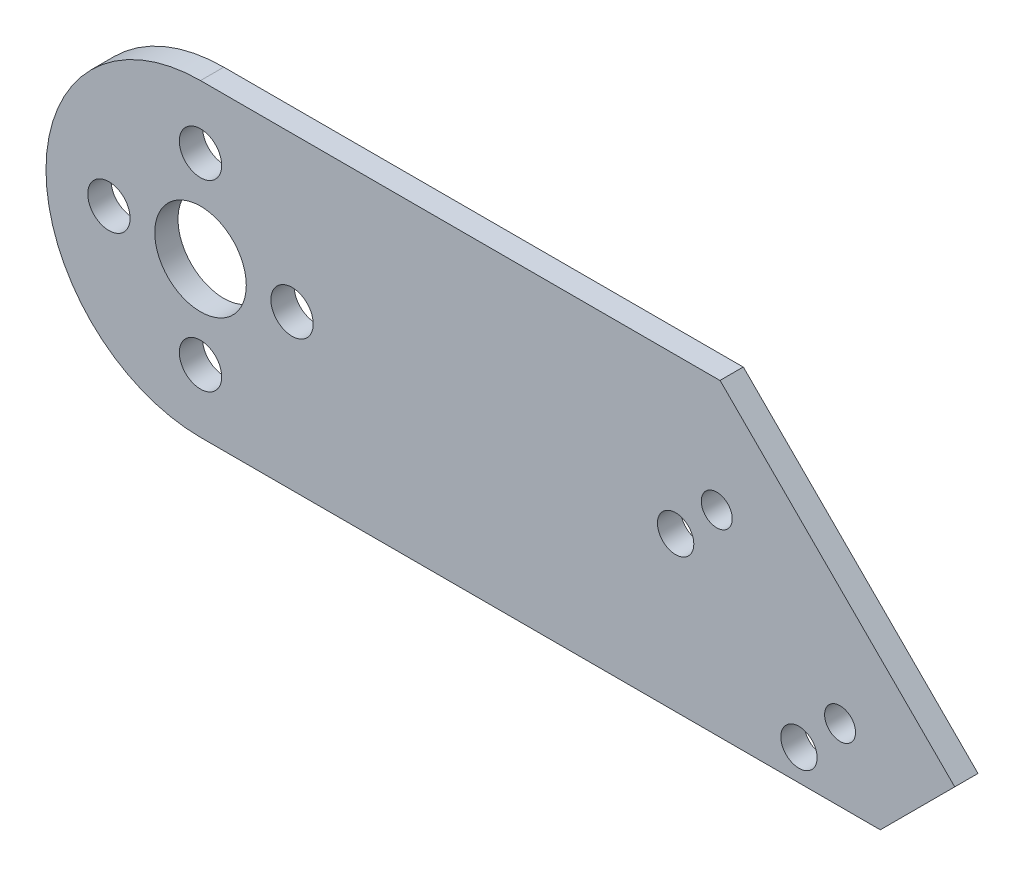
SolidWorks part; units mm, degrees
note: '?' marks a value the reader was unsure of.
ref_plane "Front" through (0, 0, 0) normal (0, 0, 1) x (1, 0, 0)
ref_plane "Top" through (0, 0, 0) normal (0, 1, 0) x (1, 0, 0)
ref_plane "Right" through (0, 0, 0) normal (1, 0, 0) x (0, 0, -1)
ref_axis "side-side" through (80.9, 0, 0) along (-1, 0, 0)?
ref_axis "up-down" through (0, 50, 0) along (0, -1, 0)?
ref_axis "front-back" through (0, 0, -80.9) along (0, 0, 1)?
sketch "Sketch1" plane through (0, 0, 0) normal (0, 0, 1) x (1, 0, 0)
  line L10 (45.3962, 13.5101) -> (45.3862, 13.5)
  line L11 (65.9023, -6.996) -> (45.3962, 13.5101)
  line L12 (59.3984, -13.5) -> (65.9023, -6.996)
  line L13 (0, -13.5) -> (59.3984, -13.5)
  line L14 (45.3862, 13.5) -> (0, 13.5)
  arc A2 (0, 13.5) -> (0, -13.5) centre (0, 0) ccw
  circle A7 centre (8, 0) radius 1.85
  circle A8 centre (0, 8) radius 1.85
  circle A9 centre (-8, 0) radius 1.85
  circle A10 centre (0, -8) radius 1.85
  circle A11 centre (0, 0) radius 4
  circle A14 centre (45.107, 3.5618) radius 1.3525
  circle A15 centre (55.8833, -7.2145) radius 1.3525
sketch "Sketch2" plane through (0, 0, 0) normal (0, 0, 1) x (1, 0, 0)
  line L5 (45.3962, 13.5101) -> (45.3862, 13.5)
  line L6 (45.3862, 13.5) -> (0, 13.5)
  line L7 (0, -13.5) -> (59.3984, -13.5)
  line L8 (59.3984, -13.5) -> (65.9023, -6.996)
  line L9 (65.9023, -6.996) -> (45.3962, 13.5101)
  line L10 (45.3962, 13.5101) -> (45.3862, 13.5)
  line L11 (45.3862, 13.5) -> (0, 13.5)
  line L12 (0, -13.5) -> (59.3984, -13.5)
  line L13 (59.3984, -13.5) -> (65.9023, -6.996)
  line L14 (65.9023, -6.996) -> (45.3962, 13.5101)
  circle A0 centre (41.5149, -0.0303) radius 1.5875 construction
  circle A1 centre (8, 0) radius 1.85
  circle A2 centre (8, 0) radius 1.85
  arc A3 (0, 13.5) -> (0, -13.5) centre (0, 0) ccw
  arc A4 (0, 13.5) -> (0, -13.5) centre (0, 0) ccw
  circle A5 centre (55.8833, -7.2145) radius 1.3525
  circle A6 centre (55.8833, -7.2145) radius 1.3525
  circle A7 centre (45.107, 3.5618) radius 1.3525
  circle A8 centre (45.107, 3.5618) radius 1.3525
  circle A9 centre (0, 0) radius 4
  circle A10 centre (0, 0) radius 4
  circle A11 centre (0, -8) radius 1.85
  circle A12 centre (0, -8) radius 1.85
  circle A13 centre (-8, 0) radius 1.85
  circle A14 centre (-8, 0) radius 1.85
  circle A15 centre (0, 8) radius 1.85
  circle A16 centre (0, 8) radius 1.85
  circle A17 centre (52.2912, -10.8066) radius 1.5875 construction
  circle A18 centre (41.5149, -0.0303) radius 1.5875
  circle A19 centre (52.2912, -10.8066) radius 1.5875
  dimension "D1" = 0
  dimension "D2" = 0
  dimension "D3" = 0
  dimension "D4" = 0
  dimension "D5" = 0
  dimension "D6" = 0
  dimension "D7" = 0
  dimension "D8" = 0
extrude "Boss-Extrude1" add sketch "Sketch2" along normal blind 2.032
hole_wizard "#6 Clearance Hole1" [suppressed] positions "Sketch4" profile "Sketch3" hole size "#6" standard "ANSI Inch"
sketch "Sketch4" plane through (0, 0, 2.032) normal (0, 0, 1) x (1, 0, 0)
  point P0 (45.107, 3.5618)
  point P2 (55.8833, -7.2145)
sketch "Sketch3" plane through (45.107, 3.5618, 2.032) normal (1, 0, 0) x (0, -1, 0)
  line L0 (0, 0) -> (0, 2.032)
  line L1 (0, 2.032) -> (1.8986, 2.032)
  line L2 (1.8986, 2.032) -> (1.8986, 0)
  line L5 (1.8986, 0) -> (0, 0)
  line L11 (0, -6.35) -> (0, 107.95) construction
  dimension "Thru Hole Dia." = 3.7973
  dimension "Thru Hole Depth" = 2.032
